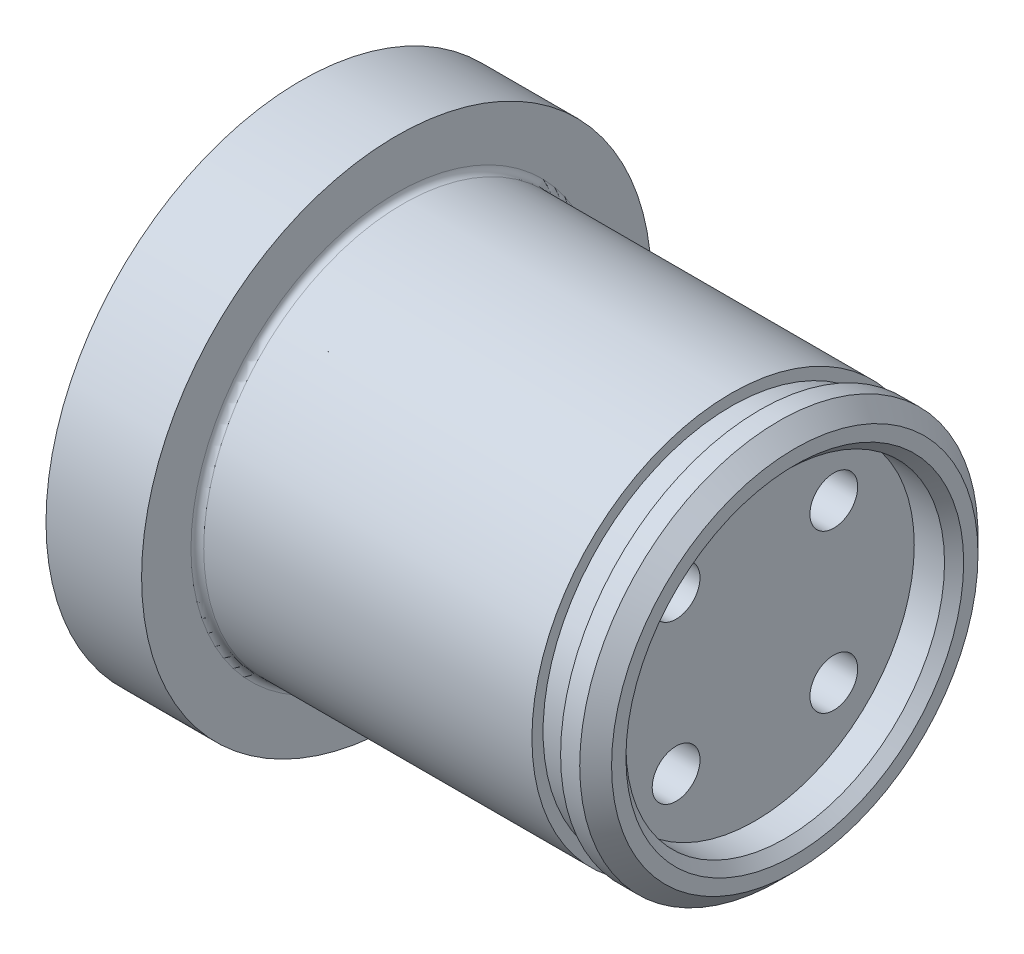
SolidWorks part; units mm, degrees
material "1060 Сплав"
ref_plane "Спереди" through (0, 0, 0) normal (0, 0, 1) x (1, 0, 0)
ref_plane "Сверху" through (0, 0, 0) normal (0, 1, 0) x (1, 0, 0)
ref_plane "Справа" through (0, 0, 0) normal (1, 0, 0) x (0, 0, -1)
sketch "Эскиз1" plane through (0, 0, 0) normal (0, 0, 1) x (1, 0, 0)
  line L0 (0, 0) -> (22138.4448, 0) construction
  line L1 (0, 0) -> (0, 12.5)
  line L2 (0, 12.5) -> (-25, 12.5)
  line L3 (-25, 12.5) -> (-25, 16)
  line L4 (-25, 16) -> (-31, 16)
  line L5 (-31, 16) -> (-31, 0)
  line L8 (0, 0) -> (-31, 0)
  dimension "D1" = 31
  dimension "D2" = 6
  dimension "D3" = 25
  dimension "D6" = 32
revolve "Повернуть1" add sketch "Эскиз1" angle 360 about L0
sketch "Эскиз2" plane through (0, 0, 0) normal (0, 0, 1) x (1, 0, 0)
  line L0 (-4, 12.5) -> (-4, 11.8)
  line L1 (0, 12.5) -> (-25, 12.5) construction
  line L2 (-4, 11.8) -> (-2.2, 11.8)
  line L3 (-2.2, 11.8) -> (-2.2, 12.5)
  line L4 (-2.2, 12.5) -> (-4, 12.5)
  line L5 (0, -12.5) -> (0, 12.5) construction
  line L6 (0, 0) -> (-50000, 0) construction
  point P10 (-2.2, 12.15)
  point P13 (0, 0)
  dimension "D1" = 4
  dimension "D2" = 1.8
  dimension "D3" = 23.6
revolve "Вырез-Повернуть1" cut sketch "Эскиз2" angle 360 about L6
chamfer "Фаска1" distance 1 angle 45 1 edges at (0, 0, 12.5)
fillet "Скругление1" radius 0.4 1 edges at (-25, 0, 12.5)
hole_wizard "Отверстие1" positions "Эскиз3" profile "Эскиз4" legacy end condition through all
sketch "Эскиз3" plane through (0, 0, 0) normal (1, 0, 0) x (0, 0, -1)
  line L0 (0, 0) -> (0, 7) construction
  line L2 (0, 0) -> (4.9497, 4.9497) construction
  circle A0 centre (0, 0) radius 7 construction
  point P0 (4.9497, 4.9497)
  dimension "D1" = 14
  dimension "D2" = 45
sketch "Эскиз4" plane through (0, 4.9497, -4.9497) normal (0, 1, 0) x (0, 0, -1)
  line L0 (0, 0) -> (0, 31)
  line L1 (0, 31) -> (1.5, 31)
  line L2 (1.5, 31) -> (1.5, 0)
  line L3 (1.5, 0) -> (0, 0)
  line L4 (0, 110) -> (0, -10) construction
  dimension "Диаметр" = 3
  dimension "Глубина" = 31
pattern_circular "Круговой массив1" count 4 over 360 about axis through (0, 0, 0) along (-1, 0, 0) of "Отверстие1"
sketch "Эскиз5" plane through (0, 0, 0) normal (0, 0, 1) x (1, 0, 0)
  line L0 (0, 0) -> (0, 10)
  line L1 (0, -11.5) -> (0, 11.5) construction
  line L7 (0, 10) -> (-2.5, 10)
  line L8 (-2.5, 10) -> (-2.5, 0)
  line L9 (-2.5, 0) -> (0, 0)
  line L10 (0, 0) -> (-50000, 0) construction
  dimension "D1" = 2.5
  dimension "D2" = 20
revolve "Вырез-Повернуть2" cut sketch "Эскиз5" angle 360 about L10
chamfer "Фаска2" distance 0.6 angle 45 1 edges at (0, 0, -10)
